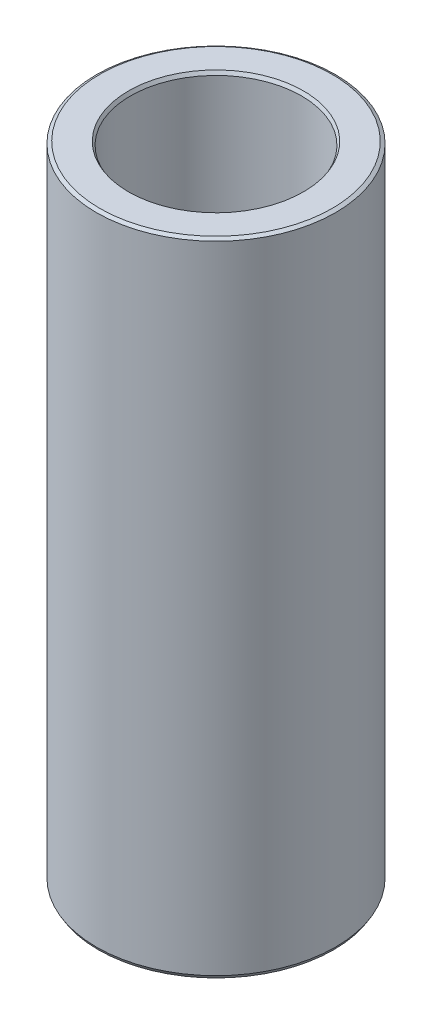
SolidWorks part; units mm, degrees
ref_plane "Front Plane" through (0, 0, 0) normal (0, 0, 1) x (1, 0, 0)
ref_plane "Top Plane" through (0, 0, 0) normal (0, 1, 0) x (1, 0, 0)
ref_plane "Right Plane" through (0, 0, 0) normal (1, 0, 0) x (0, 0, -1)
sketch "Sketch1" plane through (0, 0, 0) normal (0, 1, 0) x (1, 0, 0)
  circle A0 centre (0, 0) radius 32.5
  dimension "SLEEVE_OD" = 65
extrude "Boss-Extrude1" add sketch "Sketch1" along normal blind 174.338
sketch "Sketch2" plane through (0, 0, 0) normal (0, 1, 0) x (1, 0, 0)
  circle A0 centre (0, 0) radius 23.2568
  dimension "BORE_D" = 46.5135
extrude "Cut-Extrude1" cut sketch "Sketch2" along normal through all
chamfer "Chamfer1" distance 0.5311 angle 60 4 edges at (0, 174.338, 23.2568) (0, 0, 23.2568) (0, 0, 32.5) (0, 174.338, 32.5) first distance on face at (0, 174.338, 23.2568) first distance on face at (0, 0, 23.2568) first distance on face at (0, 174.338, 32.5)
